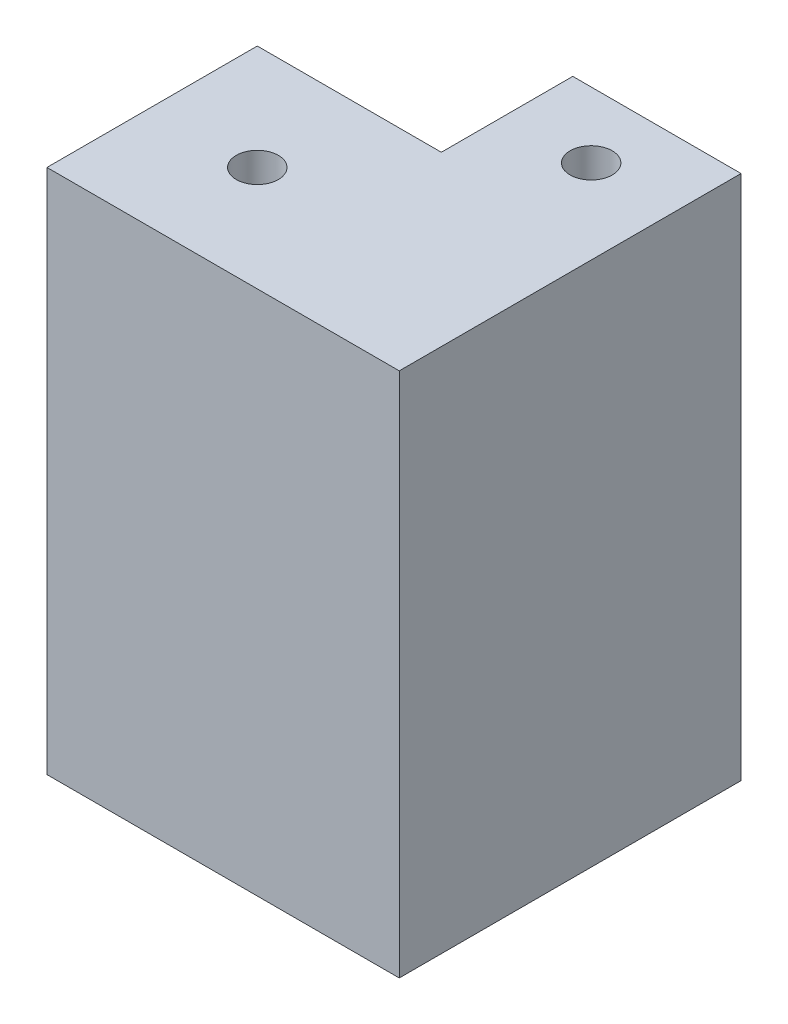
SolidWorks part; units mm, degrees
ref_plane "Front Plane" through (0, 0, 0) normal (0, 0, 1) x (1, 0, 0)
ref_plane "Top Plane" through (0, 0, 0) normal (0, 1, 0) x (1, 0, 0)
ref_plane "Right Plane" through (0, 0, 0) normal (1, 0, 0) x (0, 0, -1)
sketch "Sketch1" plane through (0, 0, 0) normal (0, 1, 0) x (1, 0, 0)
  line L19 (0, -40) -> (0, 0) construction
  line L24 (-25, 0) -> (-5, -40) construction
  line L25 (0, 25) -> (-25, 25) construction
  line L26 (-25, 25) -> (-25, 0) construction
  line L27 (0, 25) -> (32, 0) construction
  line L28 (32, 0) -> (0, 0) construction
  line L29 (-35, 0) -> (0, 0)
  line L30 (-35, -40) -> (-35, 0)
  line L31 (32, -40) -> (-35, -40)
  line L32 (32, 25) -> (32, -40)
  line L33 (0, 25) -> (32, 25)
  line L34 (0, 0) -> (0, 25)
  line L35 (-5, 5) -> (-5, -40) construction
  line L36 (-25, 25) -> (-5, 25) construction
  line L37 (-25, 25) -> (-25, 5) construction
  line L38 (-25, 5) -> (-5, 5) construction
  line L39 (-5, 25) -> (-5, 5) construction
  circle A10 centre (-15, -20) radius 16 construction
  circle A11 centre (-15, -20) radius 6.75 construction
  circle A12 centre (16, 12.5) radius 6 construction
  circle A13 centre (16, 12.5) radius 11 construction
  circle A14 centre (-15, -20) radius 4
  circle A15 centre (16, 12.5) radius 4
  point P1 (0, 0)
  dimension "D4" = 40
  dimension "D6" = 8
  dimension "D3" = 32
  dimension "D5" = 20
  dimension "D7" = 13.5
  dimension "D8" = 32
  dimension "D9" = 8
  dimension "D10" = 12
  dimension "D11" = 22
  dimension "D1" = 25
  dimension "D2" = 25
  dimension "D12" = 20
extrude "Boss-Extrude1" add sketch "Sketch1" along normal blind 100
sketch "Sketch4" plane through (0, 0, 0) normal (0, -1, 0) x (-1, 0, 0)
  point P0 (15, -20)
hole_wizard "CBORE for M5 Hex Head Bolt2" positions "Sketch4" profile "Sketch5" counterbore size "M5" standard "ANSI Metric"
sketch "Sketch5" plane through (-15, 0, 20) normal (1, 0, 0) x (0, 0, -1)
  line L0 (0, 0) -> (0, 23.85)
  line L1 (0, 23.85) -> (6.75, 23.85)
  line L2 (6.75, 23.85) -> (6.75, 5)
  line L3 (6.75, 5) -> (16, 5)
  line L4 (16, 5) -> (16, 0)
  line L5 (16, 0) -> (0, 0)
  line L10 (0, 23.85) -> (-6.75, 23.85) construction
  line L11 (0, -6.35) -> (0, 107.95) construction
  dimension "Hole Dia." = 13.5
  dimension "Hole Depth" = 23.85
  dimension "C'Bore Dia." = 32
  dimension "C'Bore Depth" = 5
  dimension "Drill Angle" = 180
sketch "Sketch6" plane through (0, 0, 0) normal (0, -1, 0) x (-1, 0, 0)
  point P0 (-16, 12.5)
hole_wizard "CBORE for M5 Hex Head Bolt3" positions "Sketch6" profile "Sketch7" counterbore size "M5" standard "ANSI Metric"
sketch "Sketch7" plane through (16, 0, -12.5) normal (1, 0, 0) x (0, 0, -1)
  line L0 (0, 0) -> (0, 13.5)
  line L1 (0, 13.5) -> (5.1, 13.5)
  line L2 (5.1, 13.5) -> (5.1, 3.5)
  line L3 (5.1, 3.5) -> (11, 3.5)
  line L4 (11, 3.5) -> (11, 0)
  line L5 (11, 0) -> (0, 0)
  line L10 (0, 13.5) -> (-5.1, 13.5) construction
  line L11 (0, -6.35) -> (0, 107.95) construction
  dimension "Hole Dia." = 10.2
  dimension "Hole Depth" = 13.5
  dimension "C'Bore Dia." = 22
  dimension "C'Bore Depth" = 3.5
  dimension "Drill Angle" = 180
